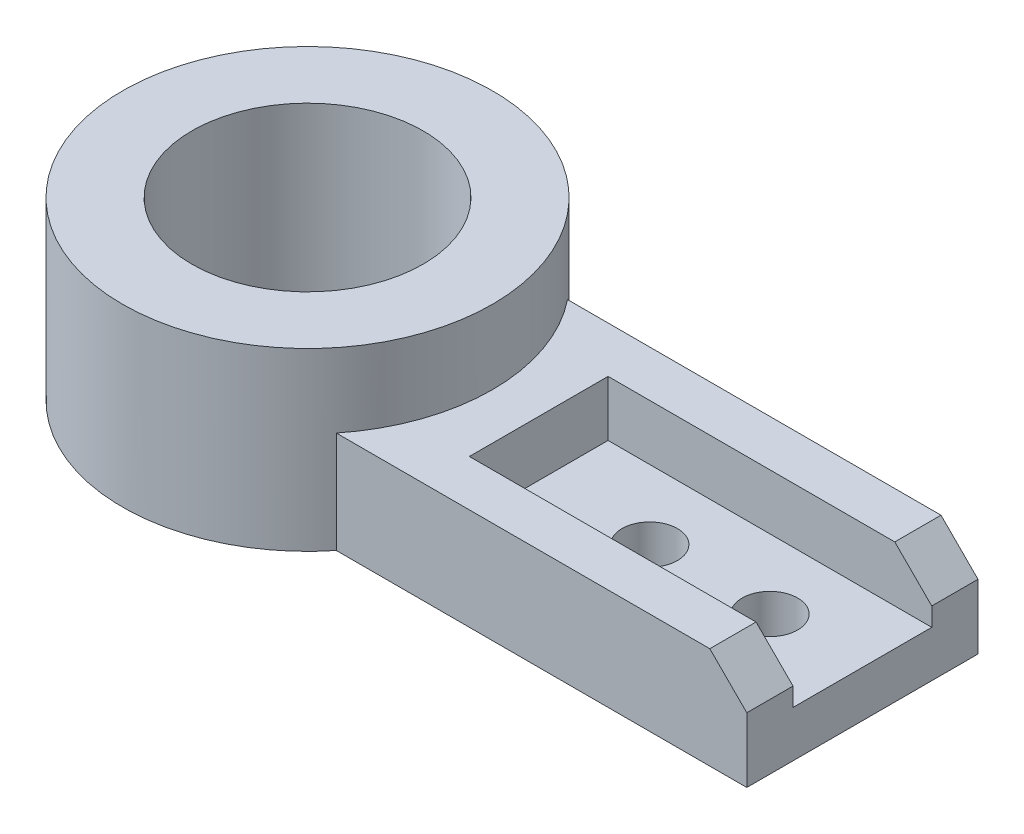
SolidWorks part; units mm, degrees
ref_plane "Front Plane" through (0, 0, 0) normal (0, 0, 1) x (1, 0, 0)
ref_plane "Top Plane" through (0, 0, 0) normal (0, 1, 0) x (1, 0, 0)
ref_plane "Right Plane" through (0, 0, 0) normal (1, 0, 0) x (0, 0, -1)
sketch "Sketch1" plane through (0, 0, 0) normal (0, 1, 0) x (1, 0, 0)
  line L0 (78.0625, 62.5) -> (300, 62.5)
  line L1 (300, 62.5) -> (300, -62.5)
  line L2 (300, -62.5) -> (78.0625, -62.5)
  line L3 (0, 0) -> (300, 0) construction
  line L4 (300, 37.5) -> (125, 37.5)
  line L5 (125, 37.5) -> (125, -37.5)
  line L6 (125, -37.5) -> (300, -37.5)
  circle A0 centre (0, 0) radius 100
  circle A1 centre (0, 0) radius 62.5
  dimension "D1" = 200
  dimension "D2" = 125
  dimension "D3" = 300
  dimension "D4" = 75
  dimension "D5" = 125
  dimension "D6" = 175
extrude "Boss-Extrude1" add sketch "Sketch1" along normal blind 25 contours L3 A0 L2 L1 L6 L5 | A0 L3 L5 L4 L1 L0 | L5 L3 L1 L4 | L3 L5 L6 L1 | A1 A0 region at (179.8633, 0, -45.2141) region at (91.6876, 0, -32.1824) region at (179.8633, 0, 45.2141) region at (212.5, 0, -18.75) region at (212.5, 0, 18.75)
extrude "Boss-Extrude2" add sketch "Sketch1<3>" along normal blind 55 contours A0 L3 L5 L4 L1 L0 | L3 A0 L2 L1 L6 L5 | A1 A0 region at (179.8633, 0, -45.2141) region at (91.6876, 0, -32.1824) region at (179.8633, 0, 45.2141)
sketch "Sketch1<3>" plane through (0, 0, 0) normal (0, 1, 0) x (1, 0, 0) same geometry as "Sketch1"
extrude "Boss-Extrude3" add sketch "Sketch1<4>" along normal blind 95 contours A1 A0 region at (91.6876, 0, -32.1824)
sketch "Sketch1<4>" plane through (0, 0, 0) normal (0, 1, 0) x (1, 0, 0) same geometry as "Sketch1"
sketch "Sketch2" plane through (0, 95, 0) normal (0, 1, 0) x (1, 0, 0)
  line L0 (-53.3854, 32.5) -> (-94.5714, 32.5)
  line L1 (94.5714, -32.5) -> (53.3854, -32.5)
  line L2 (-53.3854, -32.5) -> (-94.5714, -32.5)
  line L3 (94.5714, 32.5) -> (53.3854, 32.5)
  line L6 (0, 0) -> (-100, 0) construction
  circle A0 centre (0, 0) radius 100 construction
  arc A1 (-94.5714, 32.5) -> (-94.5714, -32.5) centre (0, 0) ccw
  circle A2 centre (0, 0) radius 62.5 construction
  arc A3 (-53.3854, 32.5) -> (-53.3854, -32.5) centre (0, 0) ccw
  arc A4 (53.3854, -32.5) -> (53.3854, 32.5) centre (0, 0) ccw
  arc A5 (94.5714, -32.5) -> (94.5714, 32.5) centre (0, 0) ccw
  dimension "D1" = 65
extrude "Boss-Extrude4" [suppressed] add sketch "Sketch2" along normal blind 20
sketch "Sketch3" plane through (0, 25, 0) normal (0, 1, 0) x (1, 0, 0)
  line L0 (300, 0) -> (125, 0) construction
  line L1 (300, 37.5) -> (300, -37.5) construction
  line L2 (125, 37.5) -> (125, -37.5) construction
  circle A0 centre (250, 0) radius 15
  circle A1 centre (185, 0) radius 15
  dimension "D1" = 30
  dimension "D2" = 50
  dimension "D3" = 65
extrude "Cut-Extrude1" cut sketch "Sketch3" against normal through all
chamfer "Chamfer1" distance 20 angle 45 2 edges at (300, 55, 50) (300, 55, -50)
